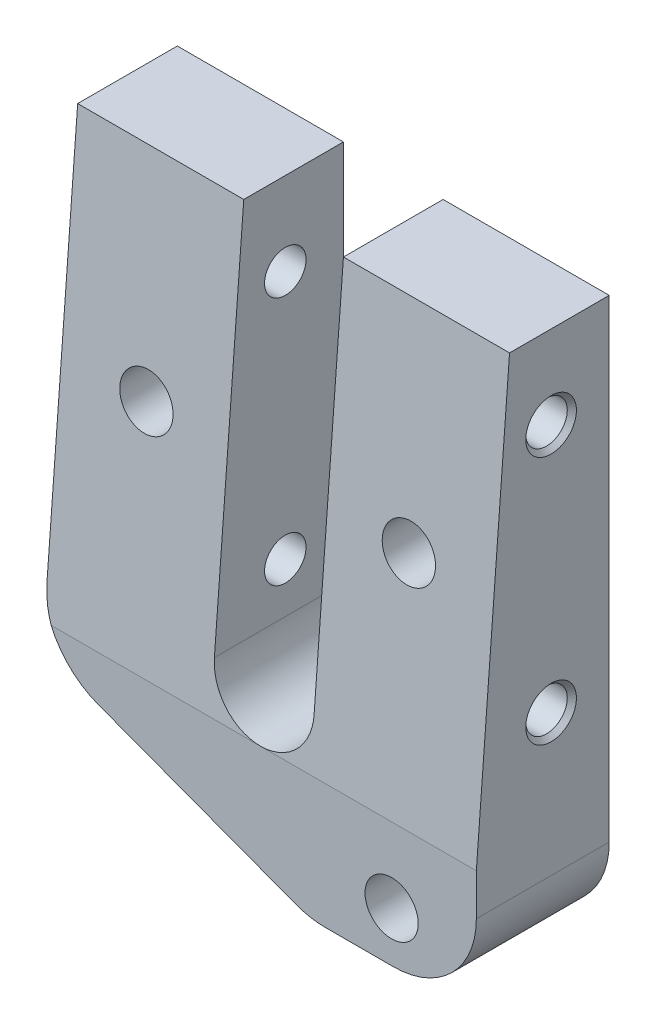
SolidWorks part; units mm, degrees
material "3.1325 (EN-AW 2017A)"
ref_plane "正面" through (0, 0, 0) normal (0, 0, 1) x (1, 0, 0)
ref_plane "平面" through (0, 0, 0) normal (0, 1, 0) x (1, 0, 0)
ref_plane "右側面" through (0, 0, 0) normal (1, 0, 0) x (0, 0, -1)
sketch "ｽｹｯﾁ2" plane through (0, 0, 0) normal (0, 0, 1) x (1, 0, 0)
  line L0 (0, 0) -> (0, 50000) construction
  line L1 (-13, 26) -> (-3, 26)
  line L2 (-3, 26) -> (-3, 0)
  line L3 (-3, 0) -> (3, 0)
  line L4 (3, 0) -> (3, 26)
  line L5 (3, 26) -> (13, 26)
  line L6 (13, 26) -> (13, -7.5)
  line L7 (13, -1.5) -> (-13, -1.5) construction
  line L8 (-13, -1.5) -> (-13, 26)
  line L9 (-13, -1.5) -> (3, -7.5)
  line L10 (3, -7.5) -> (13, -7.5)
  line L11 (7.9, 26) -> (7.9, -7.5) construction
  line L12 (-7.9, 26) -> (-7.9, -1.5) construction
  point P12 (0, -1.5)
  point P13 (0, 0)
  point P19 (-7.9, 13.5)
  point P20 (7.9, 13.5)
  point P21 (7.9, -4.5)
  dimension "D1" = 26
  dimension "D2" = 10
  dimension "D3" = 26
  dimension "D4" = 18
  dimension "D5" = 1.5
  dimension "D6" = 15.8
  dimension "D7" = 12.5
  dimension "D8" = 3
extrude "ﾎﾞｽ - 押し出し3" add sketch "ｽｹｯﾁ2" along normal blind 8
sketch "ｽｹｯﾁ1" plane through (0, 0, 0) normal (1, 0, 0) x (0, 0, -1)
  line L0 (0, 0) -> (0, 26)
  line L1 (0, 26) -> (-6, 26)
  line L2 (-6, 26) -> (-8, 0)
  line L3 (-8, 0) -> (-8, -7.5)
  line L4 (-8, -7.5) -> (0, -7.5)
  line L5 (0, -7.5) -> (0, 0)
  dimension "D1" = 6
  dimension "D2" = 8
extrude "ｶｯﾄ - 押し出し1" cut sketch "ｽｹｯﾁ1" against normal through all both and the other way through all flip side to cut
hole_wizard "M3 すきま穴1" positions "3Dｽｹｯﾁ1" profile "ｽｹｯﾁ3" hole size "M3" standard "JIS" end condition through all
sketch3d "3Dｽｹｯﾁ1"
  point P0 (7.9, 13.5, 0)
  point P2 (-7.9, 13.5, 0)
  point P4 (7.9, -4.5, 0)
sketch "ｽｹｯﾁ3" plane through (7.9, 13.5, 0) normal (1, 0, 0) x (0, 1, 0)
  line L0 (0, 0) -> (0, 8)
  line L1 (0, 8) -> (1.6, 8)
  line L2 (1.6, 8) -> (1.6, 0)
  line L5 (1.6, 0) -> (0, 0)
  line L11 (0, -6.35) -> (0, 107.95) construction
  dimension "通し穴の直径" = 3.2
  dimension "通し穴の深さ" = 8
fillet "ﾌｨﾚｯﾄ1" 2 edges at (-3, 0, 4) (3, 0, 4) type full round first side face at (-3, 13, 3.5) second side face at (3, 13, 3.5) middle face at (0, 0, 4)
fillet "ﾌｨﾚｯﾄ2" radius 5 3 edges at (3, -7.5, 4) (13, -7.5, 4) (-13, -1.5, 4)
sketch "ｽｹｯﾁ4" plane through (13, 0, 0) normal (1, 0, 0) x (0, 0, -1)
  line L0 (-3.5, 26) -> (-3.5, -9.4853) construction
  line L3 (0, -2.5) -> (0, 26) construction
  line L4 (-6, 26) -> (0, 26) construction
  point P4 (-3.5, 21)
  point P5 (-3.5, 6)
  dimension "D2" = 5
  dimension "D3" = 15
  dimension "D1" = 3.5
hole_wizard "M3x0.5 ねじ穴2" positions "ｽｹｯﾁ8" profile "ｽｹｯﾁ9" tap size "M3x0.5" standard "JIS" end condition through all
sketch "ｽｹｯﾁ8" plane through (13, 0, 0) normal (1, 0, 0) x (0, 0, -1)
  point P0 (-3.5, 21)
  point P3 (-3.5, 6)
sketch "ｽｹｯﾁ9" plane through (13, 21, 3.5) normal (0, 1, 0) x (0, 0, -1)
  line L0 (0, 0) -> (0, 26)
  line L1 (0, 26) -> (1.25, 26)
  line L2 (1.25, 26) -> (1.25, 0.275)
  line L3 (1.25, 0.275) -> (1.525, 0)
  line L5 (1.525, 0) -> (0, 0)
  line L6 (-1.25, 0.275) -> (-1.525, 0) construction
  line L11 (0, -6.35) -> (0, 107.95) construction
  dimension "ねじ山の主要直径" = 2.5
  dimension "次ｻｰﾌｪｽまでのねじ下穴ﾄﾞﾘﾙの深さ" = 26
  dimension "表面の皿穴の直径" = 3.05
  dimension "表面の皿穴の角度" = 90
